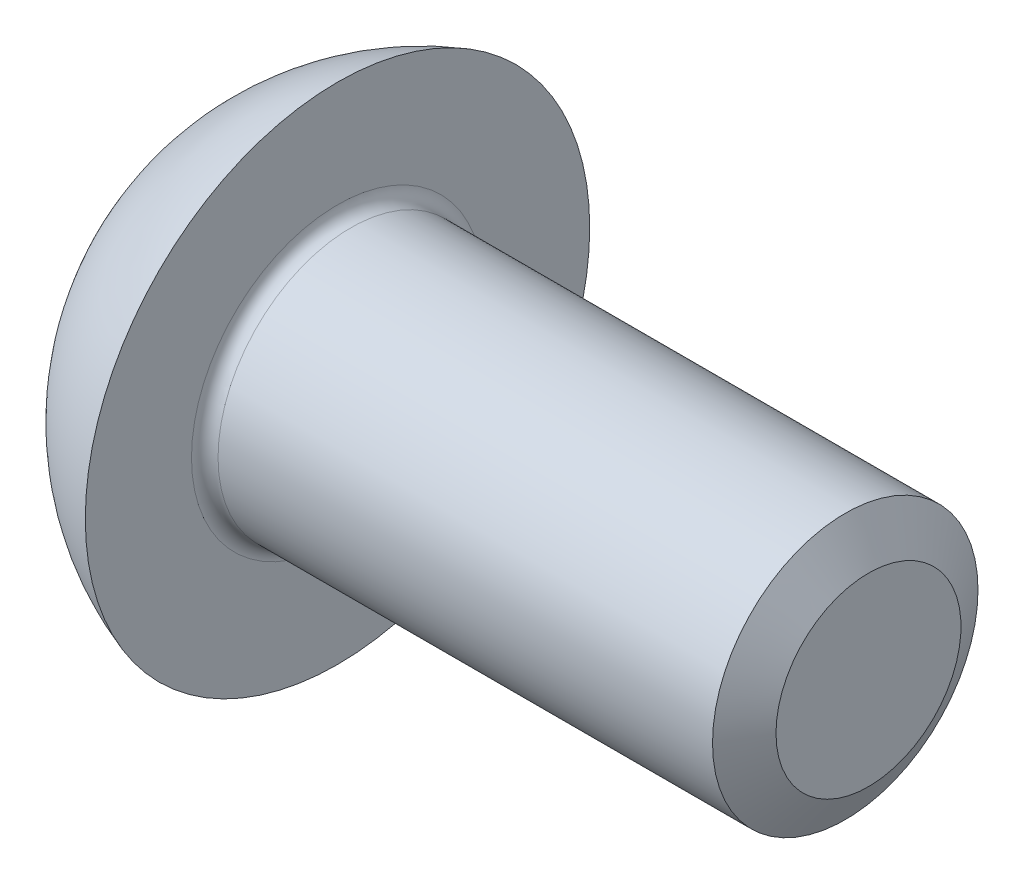
SolidWorks part; units mm, degrees
ref_plane "前视基准面" through (0, 0, 0) normal (0, 0, 1) x (1, 0, 0)
ref_plane "上视基准面" through (0, 0, 0) normal (0, 1, 0) x (1, 0, 0)
ref_plane "右视基准面" through (0, 0, 0) normal (1, 0, 0) x (0, 0, -1)
sketch "尺寸草图" plane through (0, 0, 0) normal (0, 0, 1) x (1, 0, 0)
  line L0 (0, 0) -> (8, 0) construction
  line L1 (8, 0) -> (8, 2) construction
  line L2 (8, 2) -> (7.3, 2) construction
  line L3 (0, 0) -> (0, 3.8) construction
  point P3 (1.4, 0)
  point P6 (8, 2.35)
  point P7 (0, 0.93)
  point P9 (2.2, 0)
  point P10 (2.4, 0)
  point P11 (8, 1.25)
  point P12 (3.7, 0)
  point P13 (4, 0)
  point P14 (8, 10.35)
  dimension "l" = 8
  dimension "d" = 4
  dimension "P" = 0.7
  dimension "a" = 1.4
  dimension "da" = 4.7
  dimension "dk" = 7.6
  dimension "e" = 2.87
  dimension "K" = 2.2
  dimension "r" = 0.2
  dimension "s" = 2.5
  dimension "t" = 1.3
  dimension "w" = 0.3
  dimension "zslwx" = 8
sketch "草图1" plane through (0, 0, 0) normal (0, 0, 1) x (1, 0, 0)
  line L0 (-10.2, 0) -> (0, 0) construction
  line L1 (0, 2) -> (-7.8, 2)
  line L2 (-8, 2.2) -> (-8, 3.8)
  line L3 (-10.2, 0) -> (-10.2, 2)
  line L4 (0, 2) -> (0, 0)
  line L5 (-10.2, 0) -> (0, 0)
  arc A0 (-8, 3.8) -> (-10.2, 2) centre (-6.7273, 0) ccw
  arc A1 (-7.8, 2) -> (-8, 2.2) centre (-7.8, 2.2) cw
  point P10 (-8, 2)
  dimension "r" = 0.2
  dimension "d" = 4
  dimension "dk" = 7.6
  dimension "k" = 2.2
  dimension "l" = 8
revolve "旋转1" add sketch "草图1" angle 360 about L0
cosmetic thread "装饰螺纹线1" parameters "D1"=8, "D2"=3.44
sketch "草图2" plane through (-10.2, 0, 0) normal (-1, 0, 0) x (0, 0, 1)
  line L1 (0, 1.4434) -> (-1.25, 0.7217)
  line L2 (-1.25, 0.7217) -> (-1.25, -0.7217)
  line L3 (-1.25, -0.7217) -> (0, -1.4434)
  line L4 (0, -1.4434) -> (1.25, -0.7217)
  line L5 (1.25, -0.7217) -> (1.25, 0.7217)
  line L6 (1.25, 0.7217) -> (0, 1.4434)
  circle A0 centre (0, 0) radius 1.25 construction
  dimension "s" = 2.5
extrude "切除-拉伸1" cut sketch "草图2" against normal blind 2.2
sketch "草图6" plane through (0, 0, 0) normal (0, 0, 1) x (1, 0, 0)
  line L0 (-8.9, 1.4434) -> (-8, 0)
  line L1 (-7.63, 1.4434) -> (-7.63, 0)
  line L2 (-7.63, 1.4434) -> (-8.9, 1.4434)
  line L3 (-10.2, 0) -> (-8, 0) construction
  line L4 (-7.63, 0) -> (-8, 0)
  line L5 (-10.2, 0) -> (-13.07, 0) construction
  dimension "t" = 1.3
  dimension "e-s" = 0.37
  dimension "k" = 2.2
  dimension "e" = 2.87
revolve "旋转2" add sketch "草图6" angle 360 about L3
sketch "草图7" plane through (0, 0, 0) normal (0, 0, 1) x (1, 0, 0)
  line L3 (-10.2, 1.4434) -> (-9.83, 0)
  line L4 (-10.2, 0) -> (-9.83, 0) construction
  line L7 (-10.2, 1.4434) -> (-10.2, 0)
  line L8 (-10.2, 0) -> (-9.83, 0)
  dimension "e-s" = 0.37
revolve "切除-旋转5" cut sketch "草图7" angle 360 about L4
sketch "草图4" plane through (0, 0, 0) normal (0, 0, 1) x (1, 0, 0)
  line L0 (-0.35, 2) -> (0, 1.3938)
  line L1 (-0.35, 2) -> (0.35, 2)
  line L2 (0.35, 2) -> (0, 1.3938)
  line L4 (0, -2) -> (0, 2) construction
  line L5 (-0.35, 0) -> (0.35, 0) construction
  dimension "d" = 2
  dimension "p" = 0.7
revolve "切除-旋转1" cut sketch "草图4" angle 360 about L5
ref_axis "基准轴1" through (-8.1887, 0, 0) along (1, 0, 0)
pattern_linear "阵列(线性)1" [suppressed] count 9 spacing 0.7 along (-1, 0, 0) of bodies 104
